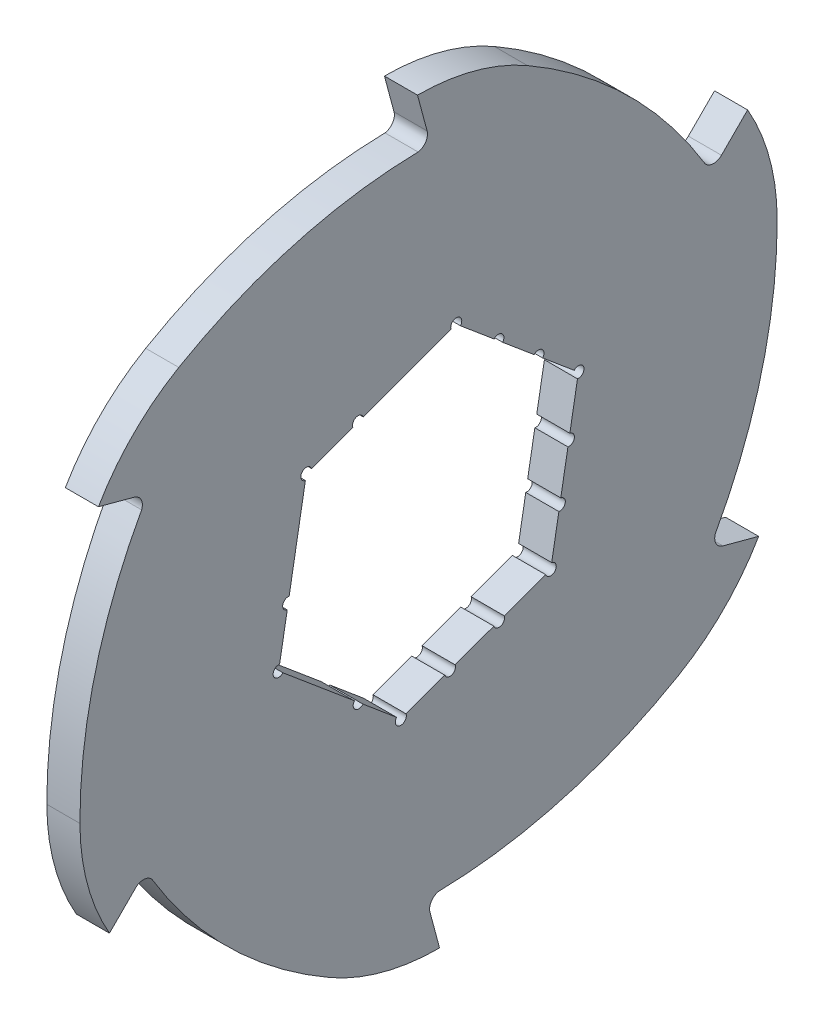
SolidWorks part; units mm, degrees
note: '?' marks a value the reader was unsure of.
material "1.0037 (S235JR)"
ref_plane "Alzado" through (0, 0, 0) normal (0, 0, 1) x (1, 0, 0)
ref_plane "Planta" through (0, 0, 0) normal (0, 1, 0) x (1, 0, 0)
ref_plane "Vista lateral" through (0, 0, 0) normal (1, 0, 0) x (0, 0, -1)
sketch "Sketch1" plane through (0, 0, 0) normal (1, 0, 0) x (0, 0, -1)
  line L0 (-56.6126, 0) -> (65.57, 0) construction
  line L1 (27.1808, 9.893) -> (5.0228, 28.4858)
  line L2 (5.0228, 28.4858) -> (-22.158, 18.5928)
  line L3 (-22.158, 18.5928) -> (-27.1808, -9.893)
  line L4 (-27.1808, -9.893) -> (-5.0228, -28.4858)
  line L5 (-5.0228, -28.4858) -> (22.158, -18.5928)
  line L6 (22.158, -18.5928) -> (27.1808, 9.893)
  circle A0 centre (0, 0) radius 25.05 construction
  circle A1 centre (0, 0) radius 59
  dimension "D2" = 118
  dimension "D1" = 50.1
  dimension "D3" = 40
extrude "Extrude1" add sketch "Sketch1" along normal mid plane 6
ref_axis "Axis1" through (-5.5, 0, 0) along (1, 0, 0)?
sketch "Sketch2" plane through (0, 0, 0) normal (1, 0, 0) x (0, 0, -1)
  line L0 (-2, 67.9618) -> (-0.2627, 61.4781)
  line L1 (0, 0) -> (0, 77.6328) construction
  line L4 (-2.1226, 58.9618) -> (0, 0) construction
  circle A0 centre (0, 0) radius 59 construction
  arc A1 (-2, 67.9618) -> (17.9271, 62.6448) centre (-2, 27.9618) cw
  arc A3 (51.2137, 29.2943) -> (-2.1226, 58.9618) centre (0, 0) ccw
  arc A4 (-0.2627, 61.4781) -> (-2.1226, 58.9618) centre (-2.1946, 60.9605) cw
  arc A5 (17.9271, 62.6448) -> (51.2137, 29.2943) centre (-26.9089, -15.3919) cw
  point P10 (-2, 67.9618)
  dimension "D2" = 40
  dimension "D4" = 2
  dimension "D3" = 9
  dimension "D6" = 90
  dimension "D1" = 15
  dimension "D5" = 2
extrude "Extrude2" add sketch "Sketch2" against normal mid plane 6
fillet "Fillet1" [suppressed] radius 0.6
pattern_circular "CirPattern1" count 6 over 360 about axis through (0, 0, 0) along (1, 0, 0) of "Extrude2", "Fillet1"
sketch "Sketch4" [suppressed] plane through (3, 0, 0) normal (1, 0, 0) x (0, 0, -1)
  circle A0 centre (0, 0) radius 67.9646 construction
  dimension "D1" = 135.9291
hole_wizard "Ø2.0 (2) Diameter Hole1" positions "Sketch5" profile "Sketch7" hole size "Ø2.0" standard "ISO" end condition up to next
sketch "Sketch5" plane through (3, 0, 0) normal (1, 0, 0) x (0, 0, -1)
  point P0 (5.0228, 28.4858)
  point P7 (27.1808, 9.893)
  point P8 (22.158, -18.5928)
  point P9 (-5.0228, -28.4858)
  point P10 (-27.1808, -9.893)
  point P11 (-22.158, 18.5928)
  dimension "D1" = 6
sketch "Sketch7" plane through (3, 28.4858, -5.0228) normal (0, 1, 0) x (0, 0, -1)
  line L0 (0, 0) -> (0, 6)
  line L1 (0, 6) -> (1, 6)
  line L2 (1, 6) -> (1, 0)
  line L5 (1, 0) -> (0, 0)
  line L11 (0, -6.35) -> (0, 107.95) construction
  dimension "Diámetro de taladro hasta el siguiente" = 2
  dimension "Profundidad de taladro hasta el siguiente" = 6
hole_wizard "Ø2.0 (2) Diameter Hole3" positions "Sketch10" profile "Sketch11" hole size "Ø2.0" standard "ISO" end condition up to next
sketch "Sketch10" plane through (3, 0, 0) normal (1, 0, 0) x (0, 0, -1)
  line L0 (5.7889, 27.843) -> (12.6642, 22.0739) construction
  line L1 (26.4148, 10.5358) -> (5.7889, 27.843) construction
  line L2 (12.6642, 22.0739) -> (19.5395, 16.3049) construction
  line L3 (19.5395, 16.3049) -> (26.4148, 10.5358) construction
  point P2 (12.6642, 22.0739)
sketch "Sketch11" plane through (3, 22.0739, -12.6642) normal (0, 1, 0) x (0, 0, -1)
  line L0 (0, 0) -> (0, 6.001)
  line L1 (0, 6.001) -> (1, 6.001)
  line L2 (1, 6.001) -> (1, 0)
  line L5 (1, 0) -> (0, 0)
  line L11 (0, -6.35) -> (0, 107.95) construction
  dimension "Diámetro de taladro hasta el siguiente" = 2
  dimension "Profundidad de taladro hasta el siguiente" = 6.001
hole_wizard "Ø2.0 (2) Diameter Hole4" positions "Sketch12" profile "Sketch13" hole size "Ø2.0" standard "ISO" end condition up to next
sketch "Sketch12" plane through (3, 0, 0) normal (1, 0, 0) x (0, 0, -1)
  line L0 (26.4148, 10.5358) -> (13.4302, 21.4312) construction
  point P0 (19.9225, 15.9835)
sketch "Sketch13" plane through (3, 15.9835, -19.9225) normal (0, 1, 0) x (0, 0, -1)
  line L0 (0, 0) -> (0, 6.001)
  line L1 (0, 6.001) -> (1, 6.001)
  line L2 (1, 6.001) -> (1, 0)
  line L5 (1, 0) -> (0, 0)
  line L11 (0, -6.35) -> (0, 107.95) construction
  dimension "Diámetro de taladro hasta el siguiente" = 2
  dimension "Profundidad de taladro hasta el siguiente" = 6.001
pattern_circular "CirPattern2" count 6 every 60 about axis through (0, 0, 0) along (1, 0, 0) of "Ø2.0 (2) Diameter Hole3"
pattern_circular "CirPattern3" count 3 every 60 about axis through (0, 0, 0) along (1, 0, 0) of "Ø2.0 (2) Diameter Hole4"
equation "\"D1@Extrude2\"=\"D1@Extrude1\""
